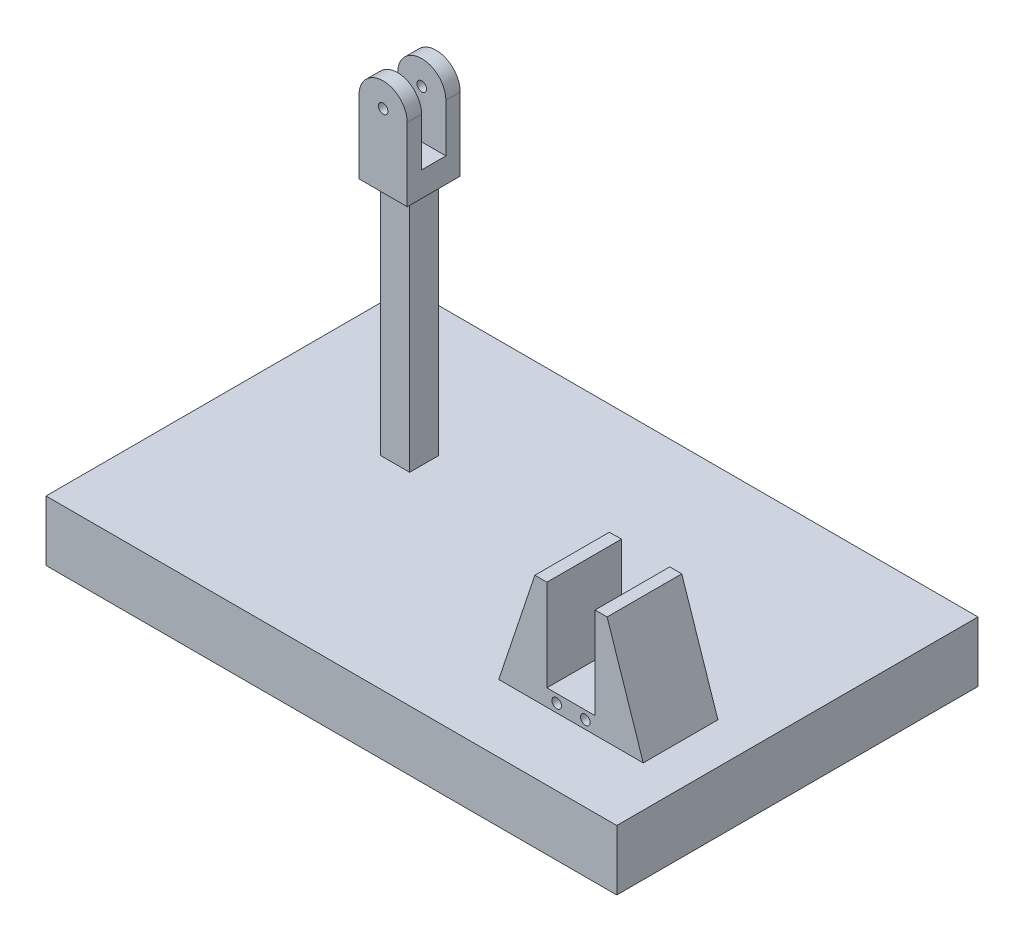
SolidWorks part; units mm, degrees
ref_plane "前基準面" through (0, 0, 0) normal (0, 0, 1) x (1, 0, 0)
ref_plane "上基準面" through (0, 0, 0) normal (0, 1, 0) x (1, 0, 0)
ref_plane "右基準面" through (0, 0, 0) normal (1, 0, 0) x (0, 0, -1)
sketch "草圖1" plane through (0, 0, 0) normal (0, 0, 1) x (1, 0, 0)
  line L0 (0, 0) -> (0, -11.05)
  line L1 (-10, 0) -> (-10, -30.2764)
  line L3 (10, -30.2764) -> (10, 0)
  line L4 (-10, -30.2764) -> (10, -30.2764)
  circle A1 centre (0, 0) radius 1.985
  arc A2 (10, 0) -> (-10, 0) centre (0, 0) ccw
  dimension "D1" = 11.05
  dimension "D2" = 3.97
  dimension "D3" = 20
extrude "填料-伸長1" add sketch "草圖1" along normal blind 12 contours L3 A2 L1 A1 region at (0, -11.3298, 0)
sketch "草圖2" plane through (10, 0, 0) normal (1, 0, 0) x (0, 0, -1)
  line L0 (-12, 0) -> (-9.1, 0)
  line L1 (-12, 0) -> (0, 0) construction
  line L2 (-12, 10) -> (-12, 0) construction
  line L3 (0, 0) -> (-2.9, 0)
  line L4 (-6, 0) -> (-3, 0)
  line L5 (-6, 0) -> (-9, 0)
  line L6 (-9, 0) -> (-9, 15.7808)
  line L7 (-9, 15.7808) -> (-3, 15.7808)
  line L8 (-3, 15.7808) -> (-3, 0)
  line L9 (-3, 0) -> (-3, -20)
  line L10 (-9, 0) -> (-8.6005, -20)
  line L11 (-8.6005, -20) -> (-3, -20)
  line M8 (0, 0) -> (-12, 0)
  dimension "D1" = 2.9
  dimension "D2" = 2.9
  dimension "D3" = 3
  dimension "D4" = 3
  dimension "D5" = 20
extrude "除料-伸長1" cut sketch "草圖2" against normal through all contours L8 L7 L6 M8 | L10 L11 L9 M8 region at (10, 7.8904, 6) region at (10, -9.8852, 5.9013)
sketch "草圖11" plane through (10, 0, 0) normal (1, 0, 0) x (0, 0, -1)
  line L0 (-9, 0) -> (-9, -20)
  line L1 (-9, -20) -> (-8.6005, -20)
  line L2 (-9, 0) -> (-8.6005, -20)
extrude "除料-伸長6" cut sketch "草圖11" against normal through all
sketch "草圖12" plane through (0, 0, 12) normal (0, 0, 1) x (1, 0, 0)
  line L0 (-10, 0) -> (-10, -30.2764)
  line L1 (-10, -30.2764) -> (10, -30.2764)
  line L2 (10, -30.2764) -> (10, 0)
  circle A0 centre (0, 0) radius 1.45
  circle A1 centre (0, 0) radius 10
  circle M1 centre (0, 0) radius 1.985
  line M2 (10, -30.2764) -> (10, 0)
  arc M3 (10, 0) -> (-10, 0) centre (0, 0) ccw
  line M4 (-10, 0) -> (-10, -30.2764)
  line M5 (-10, -30.2764) -> (10, -30.2764)
extrude "填料-伸長11" add sketch "草圖12" along normal blind 5 contours A1 M3 M1 | A1 M4 M5 M2 region at (0, -18.9541, 12) region at (0, 9.7172, 12)
sketch "草圖13" plane through (0, 0, 0) normal (0, 0, -1) x (-1, 0, 0)
  line L0 (-10, 0) -> (-10, -30.2764)
  line L1 (-10, -30.2764) -> (10, -30.2764)
  line L2 (10, 0) -> (10, -30.2764) construction
  line L3 (10, -30.2764) -> (-10, -30.2764) construction
  line L4 (10, -30.2764) -> (10, 0)
  circle A0 centre (0, 0) radius 1.45
  circle A1 centre (0, 0) radius 10
  circle M1 centre (0, 0) radius 1.985
  line M2 (-10, 0) -> (-10, -30.2764)
  line M3 (-10, -30.2764) -> (10, -30.2764)
  line M4 (10, -30.2764) -> (10, 0)
  arc M5 (10, 0) -> (-10, 0) centre (0, 0) ccw
extrude "填料-伸長12" add sketch "草圖13" along normal blind 5 contours A1 M5 M1 | A1 M2 M3 M4 region at (0, -18.9541, 0) region at (0, 9.7172, 0)
sketch "草圖14" plane through (-10, 0, 0) normal (-1, 0, 0) x (0, 0, 1)
  line L0 (3, -20) -> (0.96, -20)
  line L1 (0.96, -20) -> (0.96, 10)
  line L2 (3, 10) -> (-5, 10) construction
  line L3 (0.96, 10) -> (3, 10)
  line L5 (3, 10) -> (11.04, 10)
  line L6 (9, -20) -> (11.04, -20)
  line L7 (11.04, -20) -> (11.04, 10)
  line L8 (17, 10) -> (9, 10) construction
  line L9 (0.96, 10) -> (11.04, 10)
  line L10 (11.04, -20) -> (0.96, -20)
  line L11 (0.96, 10) -> (0.96, -20)
  line L12 (0.96, 10) -> (11.04, 10)
  line M7 (9, 0) -> (9, -20)
  line M8 (9, -20) -> (3, -20)
  line M9 (3, -20) -> (3, 0)
  line M10 (3, 0) -> (-5, 0)
  line M14 (17, 0) -> (9, 0)
  dimension "D1" = 2.04
  dimension "D2" = 2.04
extrude "除料-伸長7" cut sketch "草圖14" against normal through all contours L7 L5 L3 L1 M14 M10 M9 M8 M7 | L1 L0 M9 M10 | L6 L7 M14 M7 region at (-10, -3.1522, 6) region at (-10, -10, 1.98) region at (-10, -10, 10.02)
sketch "草圖15" plane through (0, -30.2764, 0) normal (0, -1, 0) x (1, 0, 0)
  line L0 (-10, 6) -> (10, 6)
  line L1 (-10, 17) -> (-10, -5) construction
  line L2 (10, 17) -> (10, -5) construction
  line L3 (0, 17) -> (0, -5)
  line L4 (-10, 17) -> (10, 17) construction
  line L5 (10, -5) -> (-10, -5) construction
  line L7 (-6, 0) -> (6, 0)
  line L8 (-6, 0) -> (-6, 12)
  line L9 (-6, 12) -> (6, 12)
  line L10 (6, 0) -> (6, 12)
  line L11 (-6, 0) -> (6, 12) construction
  line L12 (-6, 12) -> (6, 0) construction
  point P12 (0, 6)
  dimension "D1" = 12
  dimension "D2" = 12
extrude "填料-伸長13" add sketch "草圖15" along normal blind 100 contours L0 L10 L9 L3 | L9 L8 L0 L3 | L7 L10 L0 L3 | L8 L7 L3 L0 region at (-3, -30.2764, 9) region at (-3, -30.2764, 3) region at (3, -30.2764, 9) region at (3, -30.2764, 3)
sketch "草圖16" plane through (0, -130.2764, 0) normal (0, -1, 0) x (1, 0, 0)
  line L0 (0, 0) -> (0, 12)
  line L1 (-6, 0) -> (6, 0) construction
  line L2 (-6, 12) -> (6, 12) construction
  line L3 (0.1211, 6) -> (6, 6)
  line L4 (6, 0) -> (6, 12) construction
  line L5 (6, 6) -> (176, 6)
  line L10 (176, 6) -> (176, -54)
  line L11 (176, -54) -> (-61, -54)
  line L12 (-61, -54) -> (-61, 6)
  line L13 (-61, 6) -> (-61, 96)
  line L14 (-61, 96) -> (176, 96)
  line L15 (176, 96) -> (176, 6)
  line L16 (-6, 6) -> (-61, 6)
  line L17 (-6, 0) -> (-6, 12) construction
  point P10 (0, 6)
  line M6 (-6, 12) -> (-6, 0)
  line M7 (-6, 0) -> (6, 0)
  line M8 (6, 0) -> (6, 12)
  line M9 (6, 12) -> (-6, 12)
  dimension "D1" = 170
  dimension "D2" = 55
  dimension "D3" = 60
  dimension "D4" = 90
extrude "填料-伸長14" add sketch "草圖16" along normal blind 25 contours L16 L5 L15 L14 L13 M6 M9 M8 | L16 L12 L11 L10 L5 M6 M8 M7 | L0 M7 M9 M6 | L0 M7 M8 M9 region at (-3, -130.2764, 6) region at (57.7926, -130.2764, -24.1374) region at (0.0134, -130.2764, 6) region at (57.6948, -130.2764, 51.1423)
sketch "草圖17" plane through (0, 0, 12) normal (0, 0, 1) x (1, 0, 0)
  line L0 (0, 0) -> (0, -130.2764)
  line L1 (-6, -130.2764) -> (6, -130.2764) construction
sketch "草圖18" plane through (0, -130.2764, 0) normal (0, 1, 0) x (1, 0, 0)
  line L0 (0, -12) -> (116, -12)
  line L1 (116, -12) -> (137.15, -12)
  line L2 (116, -12) -> (94.85, -12)
  line L15 (0, -12) -> (100, -12)
  line L16 (100, -12) -> (100, -37)
  line L17 (100, -37) -> (90, -37)
  line L18 (100, -37) -> (110, -37)
  line L19 (90, -37) -> (90, -47)
  line L20 (90, -47) -> (110, -47)
  line L21 (110, -47) -> (110, -37)
  dimension "D1" = 100
  dimension "D2" = 25
  dimension "D3" = 10
  dimension "D4" = 10
  dimension "D5" = 10
sketch "草圖30" plane through (0, -130.2764, 0) normal (0, 1, 0) x (1, 0, 0)
  line L0 (0, -12) -> (129, -12)
  line L1 (116, -12) -> (137.15, -12) construction
  line L2 (129, -12) -> (129, -37)
  line L4 (129, -37) -> (139, -37)
  line L5 (129, -37) -> (119, -37)
  line L6 (119, -37) -> (119, -68)
  line L7 (119, -68) -> (139, -68)
  line L8 (139, -68) -> (139, -37)
  dimension "D1" = 129
  dimension "D2" = 10
  dimension "D3" = 10
  dimension "D4" = 31
extrude "填料-伸長19" add sketch "草圖30" along normal blind 7 contours L7 L8 L4 L5 L6 region at (129, -130.2764, 52.5)
sketch "草圖31" plane through (0, -130.2764, 0) normal (0, 1, 0) x (1, 0, 0)
  line L0 (119, -68) -> (114, -68)
  line L1 (114, -68) -> (114, -37.1297)
  line L2 (114, -37.1297) -> (119, -37)
  line L3 (119, -37) -> (119, -68)
  line L4 (139, -37) -> (139, -68)
  line L5 (139, -68) -> (144, -68)
  line L6 (144, -68) -> (144, -37)
  line L7 (144, -37) -> (139, -37)
  dimension "D1" = 5
  dimension "D2" = 5
extrude "填料-伸長20" add sketch "草圖31" along normal blind 45 contours L3 L0 L1 L2 | L7 L4 L5 L6
sketch "草圖33" plane through (0, 0, 68) normal (0, 0, 1) x (1, 0, 0)
  line L0 (114, -85.2764) -> (99, -130.2764)
  line L1 (0, -130.2764) -> (100, -130.2764) construction
  line L2 (99, -130.2764) -> (114, -130.2764)
  line L3 (0, -130.2764) -> (116, -130.2764) construction
  line L4 (116, -130.2764) -> (94.85, -130.2764) construction
  line L5 (114, -130.2764) -> (114, -85.2764)
  line L6 (144, -85.2764) -> (159, -130.2764)
  line L7 (-61, -130.2764) -> (176, -130.2764) construction
  line L8 (159, -130.2764) -> (144, -130.2764)
  line L9 (144, -85.2764) -> (144, -130.2764) construction
  line M4 (144, -130.2764) -> (144, -85.2764)
  line M10 (114, -85.2764) -> (114, -130.2764)
  dimension "D1" = 15
  dimension "D2" = 15
extrude "填料-伸長21" add sketch "草圖33" against normal blind 31 contours L8 L6 M4 | L0 L2 M10 region at (109, -115.2764, 68) region at (149, -115.2764, 68)
sketch "草圖35" plane through (0, 0, 37) normal (0, 0, -1) x (-1, 0, 0)
  line L0 (-139, -123.2764) -> (-139, -130.2764)
  line L1 (-119, -130.2764) -> (-159, -130.2764) construction
  line L2 (-139, -130.2764) -> (-119, -130.2764)
  line L3 (-119, -130.2764) -> (-119, -123.2764)
  line L4 (-119, -123.2764) -> (-139, -123.2764)
  line L5 (-139, -126.7764) -> (-119, -126.7764)
  line L6 (-129, -130.2764) -> (-129, -123.2764)
  circle A0 centre (-134.95, -126.7764) radius 2
  circle A1 centre (-123.05, -126.7764) radius 2
  point P15 (-129, -126.7764)
  dimension "D1" = 4
  dimension "D2" = 4
  dimension "D3" = 11.9
  dimension "D4" = 5.95
extrude "除料-伸長16" cut sketch "草圖35" against normal through all contours L5 A0 | L5 A0 | L5 A1 | L5 A1 region at (134.95, -125.9276, 37) region at (134.95, -127.6252, 37) region at (123.05, -125.9276, 37) region at (123.05, -127.6252, 37)
sketch "草圖37" plane through (0, -130.2764, 0) normal (0, 1, 0) x (1, 0, 0)
  line L0 (129, -68) -> (0, -68)
  line L1 (119, -68) -> (139, -68) construction
  dimension "D1" = 129
sketch "草圖38" plane through (0, -123.2764, 0) normal (0, 1, 0) x (1, 0, 0)
  line L0 (144, -52.5) -> (-6.6375, -52.5) construction
  line L1 (144, -68) -> (144, -37) construction
  line L2 (144, -78.2584) -> (-6.6375, -78.2584)
  line L3 (144, -26.7416) -> (-6.6375, -26.7416)
  line L4 (-6, -12) -> (-6, -52.5)
  line L5 (6, -12) -> (6, -52.5)
  arc A0 (144, -78.2584) -> (144, -26.7416) centre (144, -52.5) ccw
  arc A1 (-6.6375, -26.7416) -> (-6.6375, -78.2584) centre (-6.6375, -52.5) ccw
  point P4 (68.6813, -52.5)
